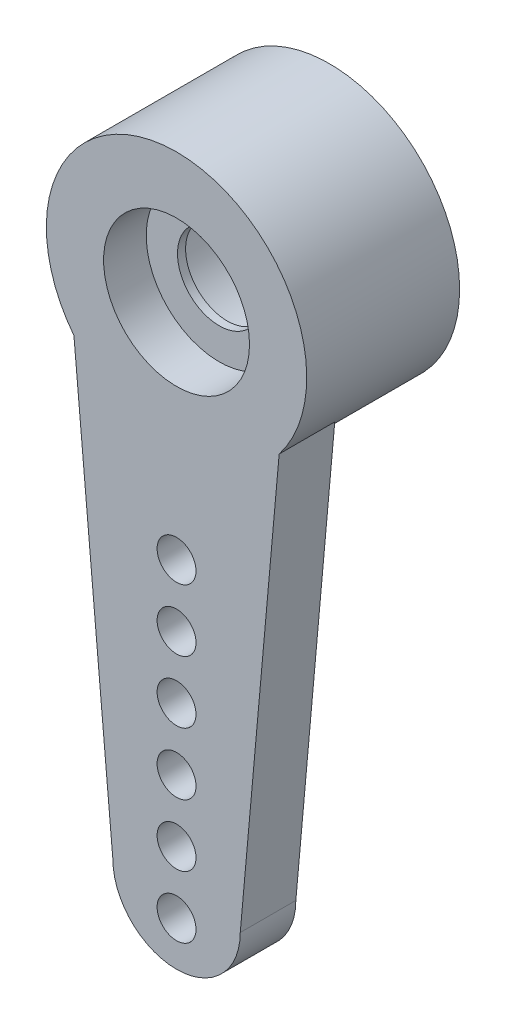
SolidWorks part; units mm, degrees
material "Nylon 6/10"
ref_plane "Front Plane" through (0, 0, 0) normal (0, 0, 1) x (1, 0, 0)
ref_plane "Top Plane" through (0, 0, 0) normal (0, 1, 0) x (1, 0, 0)
ref_plane "Right Plane" through (0, 0, 0) normal (1, 0, 0) x (0, 0, -1)
ref_plane "Plane1" through (0, 0, -7.033) normal (0, 0, 1) x (1, 0, 0)
sketch "Sketch1" plane through (0, 0, -7.033) normal (0, 0, 1) x (1, 0, 0)
  circle A0 centre (-5.5, 0) radius 3.5687
  circle A1 centre (-5.5, 0) radius 2
  dimension "D1" = 7.1374
extrude "Boss-Extrude1" add sketch "Sketch1" along normal blind 4.191
sketch "Sketch5" plane through (0, 0, -4.233) normal (0, 0, 1) x (1, 0, 0)
  circle A0 centre (-5.5, 0) radius 1.143
  circle A1 centre (-5.5, 0) radius 2 construction
  circle A2 centre (-5.5, 0) radius 2
  dimension "D1" = 2.286
extrude "Boss-Extrude2" add sketch "Sketch5" along normal offset from surface (0.2226 mm away) 1.1684 up to face at (-1.9313, 0, -2.842)
sketch "Sketch6" plane through (0, 0, -2.842) normal (0, 0, 1) x (1, 0, 0)
  line L0 (-3.7537, -14.0907) -> (-2.6869, -2.196)
  line L1 (-7.2462, -14.0907) -> (-8.313, -2.196)
  line L2 (-5.5, 0) -> (-5.5, -14.0907) construction
  line L3 (-5.5, -14.6241) -> (-5.5, -12.9223) construction
  arc A0 (-7.2462, -14.0907) -> (-3.7537, -14.0907) centre (-5.5, -14.0907) ccw
  circle A1 centre (-5.5, 0) radius 3.5687 construction
  circle A2 centre (-5.5, 0) radius 3.5687 construction
  circle A3 centre (-5.5, -12.9223) radius 0.5334
  circle A4 centre (-5.5, -14.6241) radius 0.5334
  circle A5 centre (-5.5, -11.2205) radius 0.5334
  circle A6 centre (-5.5, -9.5186) radius 0.5334
  circle A7 centre (-5.5, -7.8169) radius 0.5334
  circle A8 centre (-5.5, -6.1151) radius 0.5334
  arc A9 (-2.6869, -2.196) -> (-8.313, -2.196) centre (-5.5, 0) cw
  dimension "D1" = 3.4925
  dimension "D2" = 15.8369
  dimension "D4" = 1.0668
  dimension "D3" = 5.6261
  dimension "D6" = 1.7018
  dimension "D5" = 6
extrude "Boss-Extrude3" add sketch "Sketch6" against normal blind 1.524
scale "Scale1" bodies to scale 103 scale about centroid uniform scaling yes scale factor 0.1
sketch "Sketch9" plane through (0, 0, -4.6762) normal (0, 0, -1) x (-1, 0, 0)
  line L0 (5.5, -2.6465) -> (5.5, -4.4124)
  circle A0 centre (5.5, -3.0033) radius 0.3569 construction
ref_plane "Plane2" through (-5.5, 0, 0) normal (1, 0, 0) x (0, -1, 0)
scale "Scale2" bodies to scale 104 scale about centroid uniform scaling yes scale factor 10
